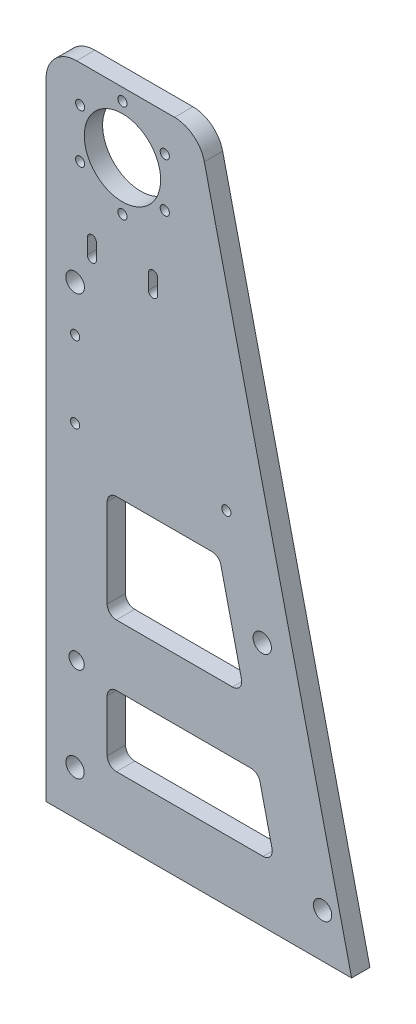
SolidWorks part; units mm, degrees
material "Policarbonato"
ref_plane "Plano frontal" through (0, 0, 0) normal (0, 0, 1) x (1, 0, 0)
ref_plane "Plano superior" through (0, 0, 0) normal (0, 1, 0) x (1, 0, 0)
ref_plane "Plano direito" through (0, 0, 0) normal (1, 0, 0) x (0, 0, -1)
sketch "Esboço1" plane through (0, 0, 0) normal (0, 0, 1) x (1, 0, 0)
  line L0 (0, 0) -> (0, 215)
  line L2 (100, 0) -> (0, 0)
  line L3 (0, 215) -> (50, 215)
  line L4 (50, 215) -> (100, 0)
  line L5 (10, 75.4302) -> (10, 15) construction
  line L6 (25, 215) -> (25, 175) construction
  line L7 (10, 15) -> (85.7122, 15) construction
  line L8 (85.7122, 15) -> (71.6586, 75.4302) construction
  line L9 (71.6586, 75.4302) -> (10, 75.4302) construction
  line L10 (20, 95) -> (20, 66)
  line L11 (23, 63) -> (61.0374, 63)
  line L12 (63.9594, 66.6795) -> (57.2152, 95.6795)
  line L13 (54.2932, 98) -> (23, 98)
  line L14 (20, 40) -> (20, 23)
  line L15 (23, 20) -> (71.0374, 20)
  line L16 (73.9594, 23.6795) -> (70.0059, 40.6795)
  line L17 (23, 43) -> (67.0839, 43)
  circle A0 centre (25, 195) radius 12.5
  circle A1 centre (25, 195) radius 16 construction
  circle A2 centre (25, 211) radius 1.5
  arc A8 (70.0059, 40.6795) -> (67.0839, 43) centre (67.0839, 40) ccw
  arc A9 (71.0374, 20) -> (73.9594, 23.6795) centre (71.0374, 23) ccw
  arc A10 (20, 23) -> (23, 20) centre (23, 23) ccw
  arc A11 (20, 40) -> (23, 43) centre (23, 40) cw
  arc A12 (57.2152, 95.6795) -> (54.2932, 98) centre (54.2932, 95) ccw
  arc A13 (61.0374, 63) -> (63.9594, 66.6795) centre (61.0374, 66) ccw
  arc A14 (20, 66) -> (23, 63) centre (23, 66) ccw
  arc A15 (20, 95) -> (23, 98) centre (23, 95) cw
  circle A16 centre (38.8564, 203) radius 1.5
  circle A17 centre (38.8564, 187) radius 1.5
  circle A18 centre (25, 179) radius 1.5
  circle A19 centre (11.1436, 187) radius 1.5
  circle A20 centre (11.1436, 203) radius 1.5
  circle A21 centre (10, 45) radius 2.5
  point P26 (22.5, 105)
  point P49 (20, 63)
  point P55 (25, 175)
  point P56 (25, 195)
  dimension "D3" = 20
  dimension "D4" = 25
  dimension "D6" = 32
  dimension "D7" = 3
  dimension "D21" = 3
  dimension "D15" = 10
  dimension "D16" = 45
  dimension "D17" = 5
  dimension "D1" = 215
  dimension "D2" = 100
  dimension "D5" = 50
  dimension "D9" = 25
  dimension "D10" = 6
  dimension "D11" = 20
  dimension "D12" = 20
  dimension "D13" = 15
  dimension "D14" = 20
  dimension "D18" = 10
  dimension "D20" = 20
  dimension "D22" = 23
  dimension "D8" = 35
extrude "Ressalto-extrusão2" add sketch "Esboço1" along normal blind 6
fillet "Filete1" radius 10 2 edges at (0, 215, 3) (50, 215, 3)
sketch "Esboço2" plane through (0, 0, 6) normal (0, 0, 1) x (1, 0, 0)
  line L0 (0, 0) -> (100, 0) construction
  line L1 (0, 205) -> (0, 0) construction
  line L2 (15, 164.21) -> (35, 164.21) construction
  line L3 (15, 161.71) -> (15, 166.71) construction
  line L4 (13.5, 161.71) -> (13.5, 166.71)
  line L5 (16.5, 161.71) -> (16.5, 166.71)
  line L6 (35, 161.71) -> (35, 166.71) construction
  line L7 (33.5, 161.71) -> (33.5, 166.71)
  line L8 (36.5, 161.71) -> (36.5, 166.71)
  circle A0 centre (9.5, 137) radius 1.5
  circle A1 centre (90.5, 14.5) radius 3
  circle A2 centre (9.5, 112) radius 1.5
  circle A3 centre (9.5, 152) radius 3.05
  circle A4 centre (15, 164.21) radius 1.5 construction
  circle A5 centre (35, 164.21) radius 1.5 construction
  arc A6 (13.5, 161.71) -> (16.5, 161.71) centre (15, 161.71) ccw
  arc A7 (16.5, 166.71) -> (13.5, 166.71) centre (15, 166.71) ccw
  arc A8 (33.5, 161.71) -> (36.5, 161.71) centre (35, 161.71) ccw
  arc A9 (36.5, 166.71) -> (33.5, 166.71) centre (35, 166.71) ccw
  circle A10 centre (59, 112) radius 1.5
  circle A11 centre (9.5, 14.5) radius 3
  point P2 (9.5, 112)
  point P3 (9.5, 137)
  point P18 (25, 195)
  point P20 (25, 164.21)
  point P22 (15, 164.21)
  point P30 (35, 164.21)
  point P40 (0, 0)
  dimension "D4" = 3
  dimension "D7" = 6
  dimension "D8" = 6.1
  dimension "D10" = 3
  dimension "D14" = 49.5
  dimension "D15" = 9.5
  dimension "D1" = 112
  dimension "D2" = 25
  dimension "D3" = 9.5
  dimension "D5" = 14.5
  dimension "D6" = 9.5
  dimension "D9" = 15
  dimension "D11" = 20
  dimension "D12" = 30.79
  dimension "D13" = 5
extrude "Corte-extrusão1" cut sketch "Esboço2" against normal through all
sketch "Esboço3" plane through (0, 0, 6) normal (0, 0, 1) x (1, 0, 0)
  circle A1 centre (70.7598, 80.3986) radius 3
extrude "Corte-extrusão2" cut sketch "Esboço3" against normal through all
